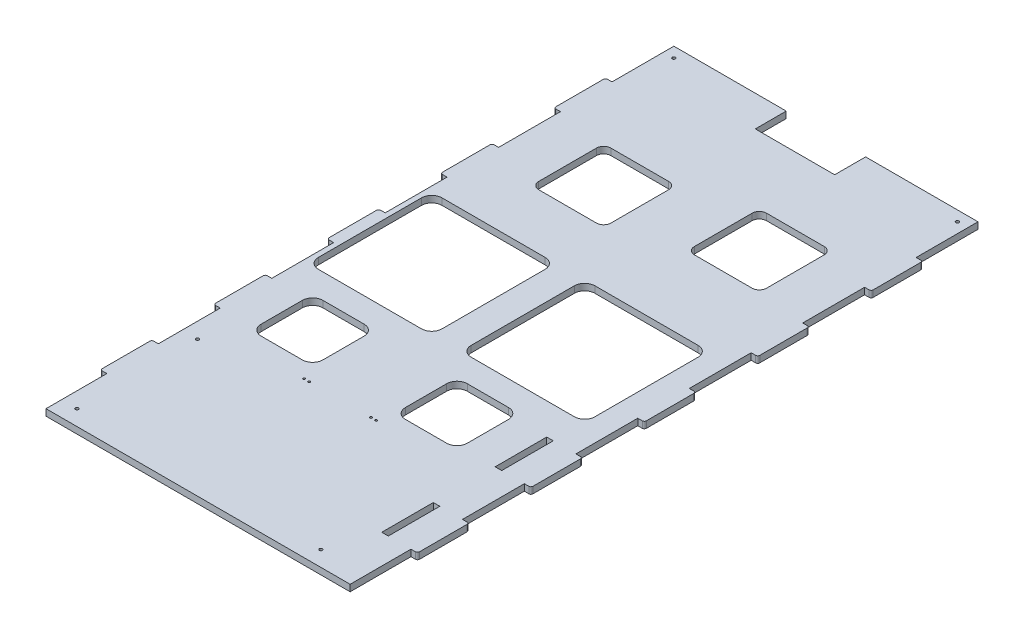
SolidWorks part; units mm, degrees
material "Beech"
ref_plane "Front Plane" through (0, 0, 0) normal (0, 0, 1) x (1, 0, 0)
ref_plane "Top Plane" through (0, 0, 0) normal (0, 1, 0) x (1, 0, 0)
ref_plane "Right Plane" through (0, 0, 0) normal (1, 0, 0) x (0, 0, -1)
sketch "Sketch1" plane through (0, 0, 0) normal (0, 1, 0) x (1, 0, 0)
  line L1 (0, 0) -> (295, 0)
  line L2 (0, 0) -> (0, 59)
  line L3 (0, 609) -> (295, 609)
  line L4 (295, 0) -> (295, 59)
  line L5 (0, 59) -> (-6.35, 59)
  line L7 (0, 109) -> (-6.35, 109)
  line L8 (-6.35, 59) -> (-6.35, 109)
  line L9 (0, 169) -> (-6.35, 169)
  line L10 (-6.35, 169) -> (-6.35, 219)
  line L11 (0, 219) -> (-6.35, 219)
  line L13 (0, 279) -> (-6.35, 279)
  line L14 (-6.35, 279) -> (-6.35, 329)
  line L15 (0, 329) -> (-6.35, 329)
  line L17 (0, 389) -> (-6.35, 389)
  line L18 (-6.35, 389) -> (-6.35, 439)
  line L19 (0, 439) -> (-6.35, 439)
  line L21 (0, 499) -> (-6.35, 499)
  line L22 (-6.35, 499) -> (-6.35, 549)
  line L23 (0, 549) -> (-6.35, 549)
  line L25 (295, 59) -> (301.35, 59)
  line L27 (295, 109) -> (301.35, 109)
  line L28 (301.35, 59) -> (301.35, 109)
  line L29 (295, 169) -> (301.35, 169)
  line L30 (301.35, 169) -> (301.35, 219)
  line L31 (295, 219) -> (301.35, 219)
  line L33 (295, 279) -> (301.35, 279)
  line L34 (301.35, 279) -> (301.35, 329)
  line L35 (295, 329) -> (301.35, 329)
  line L37 (295, 389) -> (301.35, 389)
  line L38 (301.35, 389) -> (301.35, 439)
  line L39 (295, 439) -> (301.35, 439)
  line L41 (295, 499) -> (301.35, 499)
  line L42 (301.35, 499) -> (301.35, 549)
  line L43 (295, 549) -> (301.35, 549)
  line L44 (0, 549) -> (0, 609)
  line L46 (0, 329) -> (0, 389)
  line L49 (0, 219) -> (0, 279)
  line L50 (0, 109) -> (0, 169)
  line L51 (295, 109) -> (295, 169)
  line L52 (295, 219) -> (295, 279)
  line L53 (295, 329) -> (295, 389)
  line L54 (295, 439) -> (295, 499)
  line L55 (295, 549) -> (295, 609)
  line L56 (0, 439) -> (0, 499)
  dimension "D1" = 609
  dimension "D2" = 295
  dimension "D3" = 6.35
  dimension "D4" = 50
  dimension "D5" = 59
  dimension "D7" = 60
  dimension "D8" = 50
  dimension "D9" = 6.35
  dimension "D11" = 59
  dimension "D12" = 60
  dimension "D6" = 5
  dimension "D10" = 5
extrude "Boss-Extrude1" add sketch "Sketch1" along normal blind 6.35
fillet "Fillet1" radius 2 20 edges at (301.35, 3.175, -549) (301.35, 3.175, -499) (301.35, 3.175, -439) (301.35, 3.175, -389) (301.35, 3.175, -329) (301.35, 3.175, -279) (301.35, 3.175, -219) (301.35, 3.175, -169) (301.35, 3.175, -109) (301.35, 3.175, -59) (-6.35, 3.175, -59) (-6.35, 3.175, -109) (-6.35, 3.175, -169) (-6.35, 3.175, -219) (-6.35, 3.175, -279) (-6.35, 3.175, -329) (-6.35, 3.175, -389) (-6.35, 3.175, -439) (-6.35, 3.175, -499) (-6.35, 3.175, -549)
sketch "Sketch2" plane through (0, 6.35, 0) normal (0, 1, 0) x (1, 0, 0)
  line L0 (266.65, 0) -> (266.65, 100) construction
  line L1 (0, 0) -> (295, 0) construction
  line L2 (0, 609) -> (0, 0) construction
  line L3 (295, 609) -> (295, 0) construction
  line L4 (0, 150) -> (266.65, 100) construction
  line L5 (266.65, 169) -> (266.65, 219)
  line L6 (266.65, 59) -> (273, 59)
  line L7 (266.65, 59) -> (266.65, 109)
  line L8 (266.65, 109) -> (273, 109)
  line L9 (273, 59) -> (273, 109)
  line L10 (266.65, 169) -> (273, 169)
  line L11 (273, 169) -> (273, 219)
  line L12 (266.65, 219) -> (273, 219)
  line L13 (0, 84.2124) -> (266.65, 84) construction
  line L14 (55.0424, 492.8768) -> (111.0424, 492.8768)
  line L15 (48.0424, 485.8768) -> (48.0424, 429.8768)
  line L16 (55.0424, 422.8768) -> (111.0424, 422.8768)
  line L17 (118.0424, 485.8768) -> (118.0424, 429.8768)
  line L18 (185.2335, 513.6581) -> (241.2335, 513.6581)
  line L19 (178.2335, 506.6581) -> (178.2335, 450.6581)
  line L20 (185.2335, 443.6581) -> (241.2335, 443.6581)
  line L21 (248.2335, 506.6581) -> (248.2335, 450.6581)
  line L22 (43.325, 225.298) -> (83.325, 225.298)
  line L23 (33.325, 215.298) -> (33.325, 175.298)
  line L24 (43.325, 165.298) -> (83.325, 165.298)
  line L25 (93.325, 215.298) -> (93.325, 175.298)
  line L26 (33.325, 225.298) -> (93.325, 165.298) construction
  line L27 (33.325, 165.298) -> (93.325, 225.298) construction
  line L32 (133.325, 0) -> (133.325, 609) construction
  line L33 (295, 609) -> (0, 609) construction
  line L34 (5, 369.1536) -> (125, 369.1536)
  line L35 (5, 369.1536) -> (5, 249.1536)
  line L36 (5, 249.1536) -> (125, 249.1536)
  line L37 (125, 369.1536) -> (125, 249.1536)
  line L38 (153, 369.4528) -> (273, 369.4528)
  line L39 (153, 369.4528) -> (153, 249.4528)
  line L40 (153, 249.4528) -> (273, 249.4528)
  line L41 (273, 369.4528) -> (273, 249.4528)
  line L42 (233.325, 165.298) -> (173.325, 225.298) construction
  line L43 (233.325, 225.298) -> (173.325, 165.298) construction
  line L44 (173.325, 215.298) -> (173.325, 175.298)
  line L45 (223.325, 165.298) -> (183.325, 165.298)
  line L46 (233.325, 215.298) -> (233.325, 175.298)
  line L47 (223.325, 225.298) -> (183.325, 225.298)
  line L48 (100, 150.298) -> (105, 150.298) construction
  line L49 (105, 150.298) -> (165, 150.298) construction
  line L50 (165, 150.298) -> (170, 150.298) construction
  line L51 (147.5, 609) -> (147.5, 0) construction
  line L52 (109, 609) -> (186, 609)
  line L53 (109, 609) -> (109, 579)
  line L54 (109, 579) -> (186, 579)
  line L55 (186, 609) -> (186, 579)
  line L56 (147.5, 609) -> (147.5, 579) construction
  arc A0 (48.0424, 429.8768) -> (55.0424, 422.8768) centre (55.0424, 429.8768) ccw
  arc A1 (111.0424, 422.8768) -> (118.0424, 429.8768) centre (111.0424, 429.8768) ccw
  arc A2 (111.0424, 492.8768) -> (118.0424, 485.8768) centre (111.0424, 485.8768) cw
  arc A3 (55.0424, 492.8768) -> (48.0424, 485.8768) centre (55.0424, 485.8768) ccw
  arc A4 (178.2335, 450.6581) -> (185.2335, 443.6581) centre (185.2335, 450.6581) ccw
  arc A5 (241.2335, 443.6581) -> (248.2335, 450.6581) centre (241.2335, 450.6581) ccw
  arc A6 (241.2335, 513.6581) -> (248.2335, 506.6581) centre (241.2335, 506.6581) cw
  arc A7 (185.2335, 513.6581) -> (178.2335, 506.6581) centre (185.2335, 506.6581) ccw
  arc A8 (33.325, 175.298) -> (43.325, 165.298) centre (43.325, 175.298) ccw
  arc A9 (83.325, 165.298) -> (93.325, 175.298) centre (83.325, 175.298) ccw
  arc A10 (83.325, 225.298) -> (93.325, 215.298) centre (83.325, 215.298) cw
  arc A11 (43.325, 225.298) -> (33.325, 215.298) centre (43.325, 215.298) ccw
  arc A16 (223.325, 225.298) -> (233.325, 215.298) centre (223.325, 215.298) cw
  arc A17 (183.325, 225.298) -> (173.325, 215.298) centre (183.325, 215.298) ccw
  arc A18 (183.325, 165.298) -> (173.325, 175.298) centre (183.325, 175.298) cw
  arc A19 (233.325, 175.298) -> (223.325, 165.298) centre (223.325, 175.298) cw
  circle A20 centre (15, 15) radius 1.5
  circle A21 centre (251.65, 15) radius 1.5
  circle A22 centre (15, 131.9259) radius 1.5
  circle A23 centre (10, 599) radius 1.5
  circle A24 centre (285, 599) radius 1.5
  circle A25 centre (100, 150.298) radius 1.025
  circle A26 centre (105, 150.298) radius 1.025
  circle A27 centre (165, 150.298) radius 1.025
  circle A28 centre (170, 150.298) radius 1.025
  point P33 (118.0424, 422.8768)
  point P36 (118.0424, 492.8768)
  point P39 (48.0424, 492.8768)
  point P42 (178.2335, 443.6581)
  point P47 (248.2335, 513.6581)
  point P50 (178.2335, 513.6581)
  point P51 (63.325, 195.298)
  point P74 (133.325, 84.1062)
  point P99 (203.325, 195.298)
  dimension "D10" = 7
  dimension "D11" = 7
  dimension "D16" = 10
  dimension "D17" = 70
  dimension "D22" = 3
  dimension "D25" = 3
  dimension "D28" = 3
  dimension "D18" = 3
  dimension "D31" = 3
  dimension "D40" = 2.05
  dimension "D42" = 2.05
  dimension "D43" = 2.05
  dimension "D44" = 2.05
  dimension "D1" = 100
  dimension "D2" = 150
  dimension "D3" = 6.35
  dimension "D4" = 50
  dimension "D6" = 70
  dimension "D7" = 70
  dimension "D8" = 70
  dimension "D9" = 70
  dimension "D12" = 60
  dimension "D13" = 60
  dimension "D14" = 22
  dimension "D15" = 59
  dimension "12" = 120
  dimension "D19" = 120
  dimension "D20" = 120
  dimension "D21" = 120
  dimension "D23" = 15
  dimension "D24" = 15
  dimension "D26" = 15
  dimension "D27" = 15
  dimension "D29" = 15
  dimension "D30" = 15
  dimension "D32" = 10
  dimension "D33" = 10
  dimension "D34" = 10
  dimension "D35" = 10
  dimension "D36" = 5
  dimension "D37" = 22
  dimension "D38" = 15
  dimension "D39" = 200
  dimension "D41" = 5
  dimension "D45" = 5
  dimension "D46" = 60
  dimension "D47" = 30
  dimension "D48" = 77
  dimension "D5" = 2
extrude "Cut-Extrude1" cut sketch "Sketch2" against normal blind 6.35
fillet "Fillet2" radius 10 8 edges at (125, 3.175, -249.1536) (5, 3.175, -249.1536) (5, 3.175, -369.1536) (125, 3.175, -369.1536) (153, 3.175, -249.4528) (273, 3.175, -249.4528) (273, 3.175, -369.4528) (153, 3.175, -369.4528)
